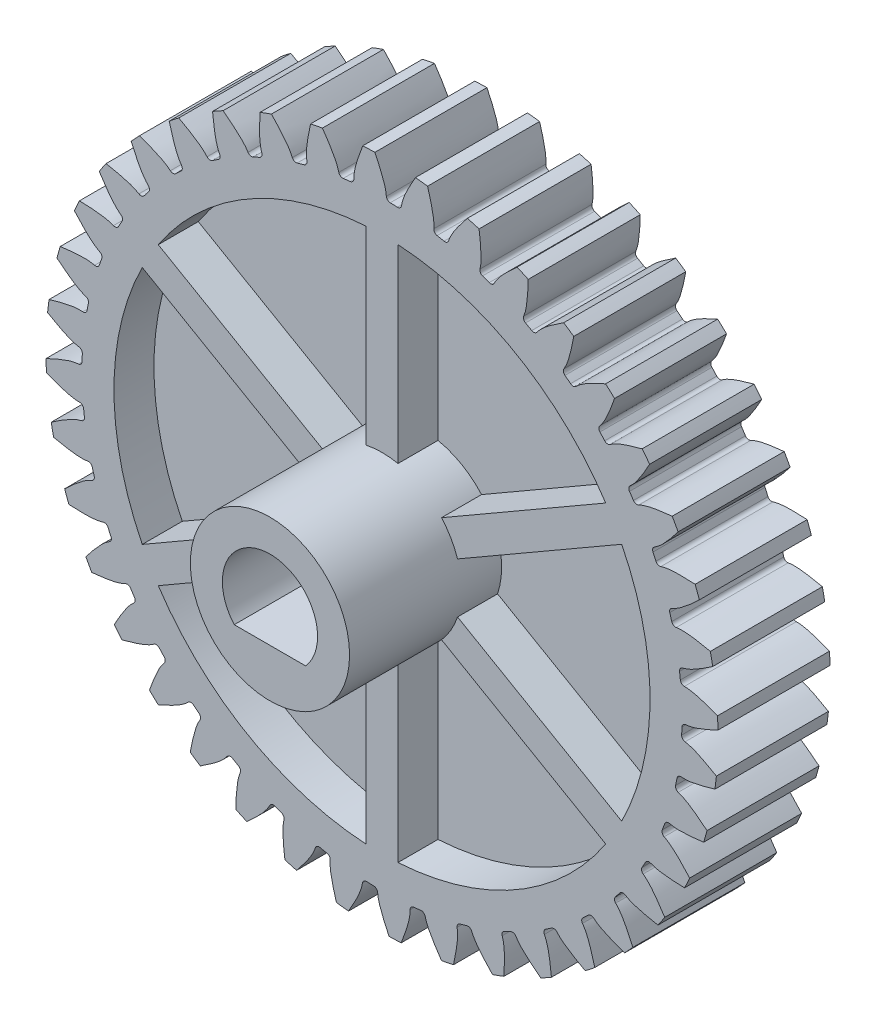
SolidWorks part; units mm, degrees
material "Acier allié"
ref_plane "Plan1" through (0, 0, 0) normal (0, 0, 1) x (1, 0, 0)
ref_plane "Plan2" through (0, 0, 0) normal (0, 1, 0) x (1, 0, 0)
ref_plane "Plan3" through (0, 0, 0) normal (1, 0, 0) x (0, 0, -1)
sketch "Esquisse1" plane through (0, 0, 0) normal (0, 0, 1) x (1, 0, 0)
  circle A0 centre (0, 0) radius 18.75
  dimension "Dp" = 37.5
sketch "Esquisse2" plane through (0, 0, 0) normal (0, 0, 1) x (1, 0, 0)
  line L0 (0, 0) -> (20.9839, 0.823) construction
  line L1 (18.7918, -0.28) -> (18.8069, 0.7376) construction
  line L2 (0, 0) -> (18.7918, -0.28) construction
  line L3 (0, 0) -> (20, 0) construction
  line L4 (0, 0) -> (20.9953, 0.4431) construction
  line L5 (20, 0) -> (20.9953, 0.4431) construction
  line L6 (17.5924, 0.0359) -> (16.6107, 0.5084) construction
  line L7 (17.0703, 1.0681) -> (17.1016, 0.2721)
  circle A0 centre (0, 0) radius 18.7938 construction
  circle A1 centre (0, 0) radius 20 construction
  circle A2 centre (0, 0) radius 21 construction
  arc A3 (20.9655, 1.2026) -> (20.9953, 0.4431) centre (0, 0) cw
  spline S0 degree 3 poles (17.1016, 0.2721) (17.2634, 0.1915) (17.7935, -0.0729) (18.7916, -0.4156) (19.9703, -0.0395) (20.6687, 0.2893) (20.9953, 0.4431) knots 0 0 0 0 0.132388 0.433806 0.735224 1 1 1 1
  spline S1 degree 3 poles (17.0703, 1.0681) (17.2253, 1.1612) (17.7331, 1.4663) (18.7014, 1.8861) (19.9058, 1.6035) (20.6279, 1.3304) (20.9655, 1.2026) knots 0 0 0 0 0.132388 0.433806 0.735224 1 1 1 1
  dimension "Db" = 37.5877
  dimension "Dn" = 40
  dimension "Dt" = 42
  dimension "Tn" = 0.854
  dimension "Tt" = 2.063
  dimension "Ts" = 2.246
extrude "Base-Extrusion" add sketch "Esquisse1" along normal mid plane 7
ref_axis "Axe1" through (0, 0, -50) along (0, 0, 1)
sketch "Esquisse9" plane through (0, 0, 3.5) normal (0, 0, 1) x (1, 0, 0)
  circle A2 centre (0, 0) radius 16.75
  circle A3 centre (0, 0) radius 16.75
  dimension "D1" = 2
extrude "Enlèv. mat.-Extru.4" cut sketch "Esquisse9" against normal offset from surface (2.5 mm away) 1 up to plane "Plan1"
mirror "Symétrie1" about plane through (0, 0, 0) normal (0, 0, 1) of "Enlèv. mat.-Extru.4"
ref_plane "Plan median" through (0, 0, 0) normal (0, 0, -1) x (-1, 0, 0)
extrude "Boss.-Extru.1" add sketch "Esquisse2" along normal mid plane 7
fillet "Congé1" radius 0.25 2 edges at (18.6685, 1.7465, 0) (18.7479, -0.279, 0)
pattern_circular "Répétition circulaire1" count 40 over 360 about axis through (0, 0, -50) along (0, 0, 1) of "Boss.-Extru.1", "Congé1"
sketch "Esquisse3" plane through (0, 0, 0) normal (0, 0, 1) x (1, 0, 0)
  circle A0 centre (0, 0) radius 2.975
  dimension "D1" = 5.95
extrude "Enlèv. mat.-Extru.2" cut sketch "Esquisse3" along normal through all both and the other way through all
sketch "Esquisse4" plane through (0, 0, -3.5) normal (0, 0, -1) x (-1, 0, 0)
  circle A0 centre (0, 0) radius 20 construction
  circle A1 centre (0, 0) radius 20
  circle A2 centre (0, 0) radius 2.975 construction
  circle A3 centre (0, 0) radius 2.975
extrude "Cylindre primitif" [suppressed] add sketch "Esquisse4" along normal up to surface (10 mm away) up to face at (0, 0, 3.5)
ref_plane "Plan médian dent" through (0, 0, 0) normal (-0.0392, 0.9992, 0) x (-0.9992, -0.0392, 0)
ref_plane "Planmédian creux" through (0, 0, 0) normal (-0.1175, 0.9931, 0) x (-0.9931, -0.1175, 0)
sketch "Esquisse5" plane through (0, 0, 0) normal (0, 0, 1) x (1, 0, 0)
  line L1 (2.2337, -1.965) -> (-2.2337, -1.965)
  circle A2 centre (0, 0) radius 4.975
  circle A3 centre (0, 0) radius 2.975 construction
  arc A5 (2.2337, -1.965) -> (-2.2337, -1.965) centre (0, 0) ccw
  point P6 (0, 2.975)
  point P9 (-3.0408, -2.027)
  point P10 (0, 0)
  dimension "D1" = 2
  dimension "D2" = 4.94
extrude "Boss.-Extru.2" add sketch "Esquisse5" along normal blind 14 from surface starting at face at (0, 0, -3.5)
sketch "Esquisse8" plane through (0, 0, 3.5) normal (0, 0, 1) x (1, 0, 0)
  line L0 (-4.3085, 2.4875) -> (-14.5059, 8.375)
  line L1 (0, 4.975) -> (0, 16.75)
  line L2 (4.3085, 2.4875) -> (14.5059, 8.375)
  line L3 (4.3085, -2.4875) -> (14.5059, -8.375)
  line L4 (0, -4.975) -> (0, -16.75)
  line L5 (-4.3085, -2.4875) -> (-14.5059, -8.375)
  circle A1 centre (0, 0) radius 16.75 construction
  circle A3 centre (0, 0) radius 4.975 construction
  point P22 (0, 0)
  dimension "D1" = 6
rib "Nervure1" sketch "Esquisse8" sketch "Esquisse8" thickness 2 extrusion direction normal to sketch draft on no parameters "D1"=2
sketch "Esquisse7" plane through (-3.0288, 0, 0) normal (0, 1, 0) x (0, 0, -1)
  line L0 (-3.5, -0.0538) -> (-10.5, -6.0038) construction
  line L2 (-3.5, -6.7493) -> (-3.5, -7.7493) construction
  line L3 (-11.9, -4.8742) -> (-11.9, -1.1834) construction
  line L4 (-11.9, -4.8742) -> (-11.9, -1.1834) construction
  line L5 (-10.5, -0.0538) -> (-10.5, -6.0038) construction
  line L6 (-11.65, -0.0538) -> (-11.65, -6.0038) construction
  line L7 (-10.5, -6.0038) -> (-3.5, -6.0038) construction
  line L12 (-11.65, -0.0538) -> (-11.65, -6.0038) construction
  line L14 (-3.5, -6.0038) -> (-3.5, -0.0538) construction
  line L15 (-10.5, -0.7951) -> (-10.5, -5.2625) construction
  line L16 (-3.5, -0.0538) -> (-10.5, -0.0538) construction
  circle A0 centre (-7, -3.0288) radius 1.65
  dimension "D2" = 3.3
extrude "Enlèv. mat.-Extru.3" [suppressed] cut sketch "Esquisse7" against normal up to next
ref_axis "Axe2" [suppressed] through (0, -7.8728, 8) along (0, 1, 0)
mirror "Symétrie3" about plane through (0, 0, 0) normal (0, 0, 1) of "Nervure1"
mirror "Symétrie2" [suppressed] about plane through (0, 0, 0) normal (0, 0, 1)
equation "\"D1@Boss.-Extru.1\"=\"D1@Base-Extrusion\""
equation "\"D1\"= \"D1@Base-Extrusion\" / 2"
equation "\"D1@Planmédian creux\"=360/2/\"D1@Répétition circulaire1\""
